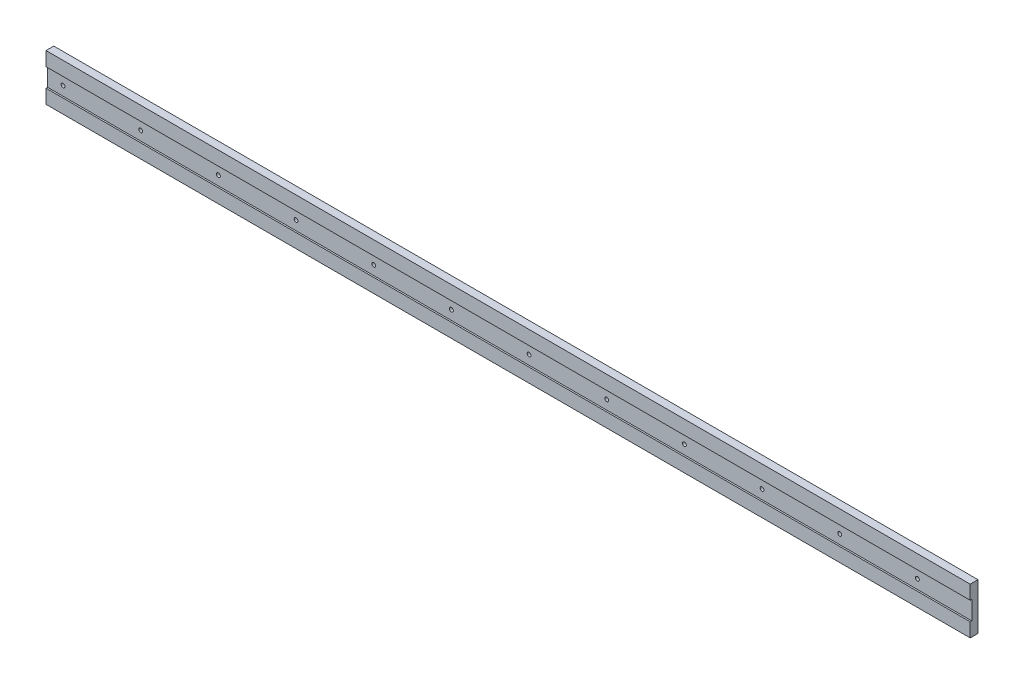
SolidWorks part; units mm, degrees
ref_plane "前视基准面" through (0, 0, 0) normal (0, 0, 1) x (1, 0, 0)
ref_plane "上视基准面" through (0, 0, 0) normal (0, 1, 0) x (1, 0, 0)
ref_plane "右视基准面" through (0, 0, 0) normal (1, 0, 0) x (0, 0, -1)
sketch "草图1" plane through (0, 0, 0) normal (0, 0, 1) x (1, 0, 0)
  line L1 (0, 0) -> (595, 0)
  line L2 (0, 0) -> (0, 30)
  line L3 (0, 30) -> (595, 30)
  line L4 (595, 0) -> (595, 30)
  dimension "D1" = 30
  dimension "D2" = 595
extrude "凸台-拉伸1" add sketch "草图1" along normal blind 5
hole_wizard "M3 螺纹孔1" positions "草图2" profile "草图3" tap size "M3" standard "ISO" end condition through all
sketch "草图2" plane through (0, 0, 5) normal (0, 0, 1) x (1, 0, 0)
  line L0 (0, 15) -> (40.9231, 15) construction
  line L1 (0, 30) -> (0, 0) construction
  point P0 (10, 15)
  point P8 (0, 0)
  dimension "D1" = 10
sketch "草图3" plane through (10, 15, 5) normal (1, 0, 0) x (0, -1, 0)
  line L0 (0, 0) -> (0, 5)
  line L1 (0, 5) -> (1.25, 5)
  line L2 (1.25, 5) -> (1.25, 0)
  line L5 (1.25, 0) -> (0, 0)
  line L11 (0, -6.35) -> (0, 107.95) construction
  dimension "通孔螺纹孔钻头直径" = 2.5
  dimension "通孔螺纹孔钻头深度" = 5
cosmetic thread "孔螺蚊线1" parameters "D2"=3
pattern_linear "阵列(线性)1" count 12 spacing 50 along (1, 0, 0) of "M3 螺纹孔1"
sketch "草图4" plane through (0, 0, 5) normal (0, 0, 1) x (1, 0, 0)
  line L0 (0, 15) -> (90.1433, 15) construction
  line L1 (0, 30) -> (0, 0) construction
  line L2 (595, 0) -> (595, 30) construction
  line L3 (0, 21) -> (595, 21)
  line L4 (0, 21) -> (0, 9)
  line L5 (0, 9) -> (595, 9)
  line L6 (595, 21) -> (595, 9)
  dimension "D1" = 12
extrude "切除-拉伸1" cut sketch "草图4" against normal blind 1
